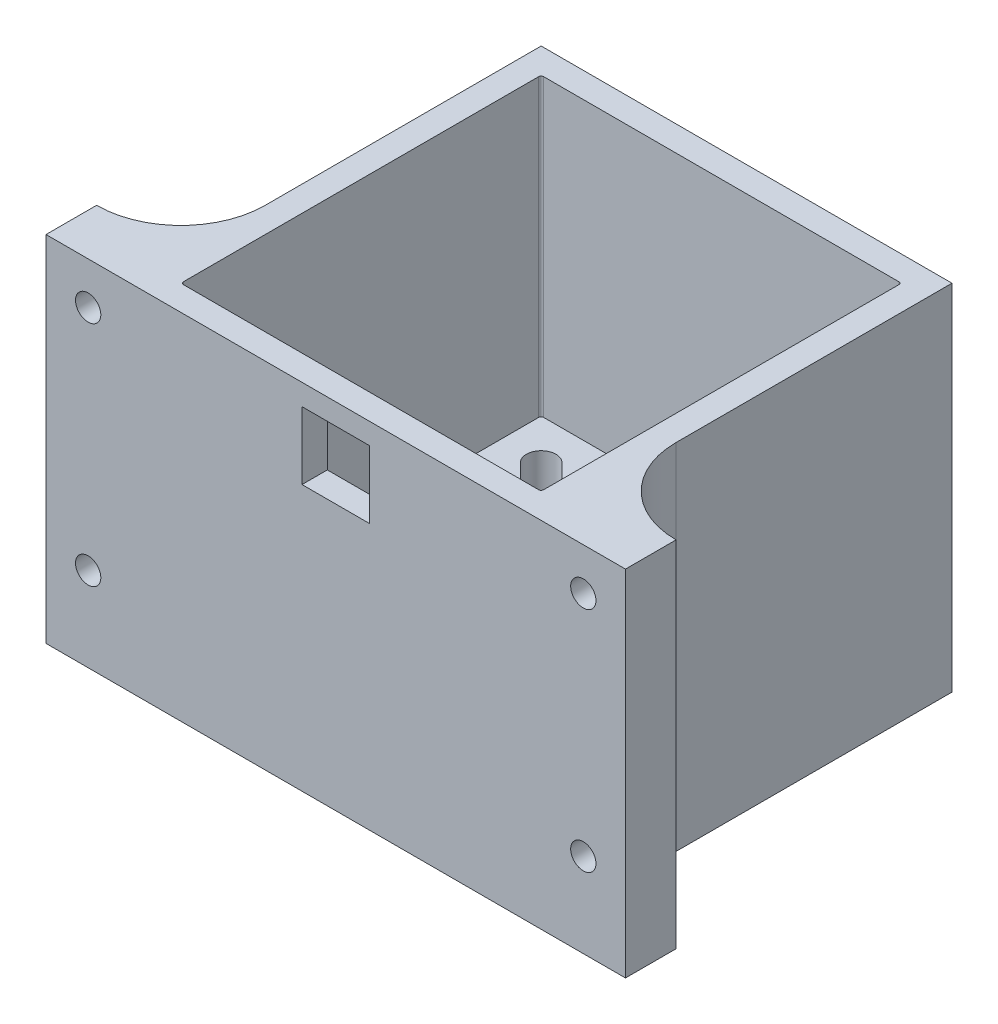
SolidWorks part; units mm, degrees
ref_plane "Front" through (0, 0, 0) normal (0, 0, 1) x (1, 0, 0)
ref_plane "Top" through (0, 0, 0) normal (0, 1, 0) x (1, 0, 0)
ref_plane "Right" through (0, 0, 0) normal (1, 0, 0) x (0, 0, -1)
sketch "Sketch1" plane through (0, 0, 0) normal (0, 1, 0) x (1, 0, 0)
  line L0 (-16.5607, 16.5607) -> (-14.4393, 14.4393) construction
  line L1 (-15.5, -15.5) -> (15.5, -15.5) construction
  line L2 (-15.5, -15.5) -> (-15.5, 15.5) construction
  line L3 (-15.5, 15.5) -> (15.5, 15.5) construction
  line L4 (15.5, -15.5) -> (15.5, 15.5) construction
  line L5 (-15.5, -15.5) -> (15.5, 15.5) construction
  line L6 (-15.5, 15.5) -> (15.5, -15.5) construction
  line L7 (-15.3232, 17.7981) -> (-13.2019, 15.6768)
  line L8 (-17.7981, 15.3232) -> (-15.6768, 13.2019)
  line L9 (0, 0) -> (0, 15.5) construction
  line L10 (0, 0) -> (15.5, 0) construction
  line L11 (16.5607, 16.5607) -> (14.4393, 14.4393) construction
  line L12 (15.3232, 17.7981) -> (13.2019, 15.6768)
  line L13 (17.7981, 15.3232) -> (15.6768, 13.2019)
  line L14 (16.5607, -16.5607) -> (14.4393, -14.4393) construction
  line L15 (15.3232, -17.7981) -> (13.2019, -15.6768)
  line L16 (17.7981, -15.3232) -> (15.6768, -13.2019)
  line L17 (-16.5607, -16.5607) -> (-14.4393, -14.4393) construction
  line L18 (-15.3232, -17.7981) -> (-13.2019, -15.6768)
  line L19 (-17.7981, -15.3232) -> (-15.6768, -13.2019)
  line L20 (21.0621, 21.3621) -> (21.3621, 21.3621) construction
  line L21 (-21.0621, -21.3621) -> (21.0621, -21.3621)
  line L22 (-21.3621, -21.0621) -> (-21.3621, 21.0621)
  line L23 (-21.0621, 21.3621) -> (21.0621, 21.3621)
  line L24 (21.3621, -21.0621) -> (21.3621, 21.0621)
  line L25 (21.3621, 21.3621) -> (21.3621, 21.0621) construction
  line L26 (-21.3621, 21.3621) -> (21.3621, -21.3621) construction
  line L27 (-21.15, -21.15) -> (21.15, -21.15) construction
  line L28 (-21.15, -21.15) -> (-21.15, 21.15) construction
  line L29 (-21.15, 21.15) -> (21.15, 21.15) construction
  line L30 (21.15, -21.15) -> (21.15, 21.15) construction
  line L31 (-21.15, -21.15) -> (21.15, 21.15) construction
  line L32 (-21.15, 21.15) -> (21.15, -21.15) construction
  line L33 (21.15, 21.15) -> (21.3621, 21.3621) construction
  line L34 (-24.3621, -21.0621) -> (-24.3621, 21.0621)
  line L35 (-21.0621, 24.3621) -> (21.0621, 24.3621)
  line L36 (24.3621, -21.0621) -> (24.3621, 21.0621)
  line L37 (-21.0621, -24.3621) -> (21.0621, -24.3621)
  line L38 (-24.3621, -21.0621) -> (-24.3621, -24.3621)
  line L39 (-24.3621, -24.3621) -> (-21.0621, -24.3621)
  line L40 (21.0621, -24.3621) -> (24.3621, -24.3621)
  line L41 (24.3621, -24.3621) -> (24.3621, -21.0621)
  line L42 (-24.3621, 21.0621) -> (-24.3621, 24.3621)
  line L43 (-24.3621, 24.3621) -> (-21.0621, 24.3621)
  line L44 (21.0621, 24.3621) -> (24.3621, 24.3621)
  line L45 (24.3621, 24.3621) -> (24.3621, 21.0621)
  arc A2 (-15.3232, 17.7981) -> (-17.7981, 15.3232) centre (-16.5607, 16.5607) ccw
  arc A3 (-15.6768, 13.2019) -> (-13.2019, 15.6768) centre (-14.4393, 14.4393) ccw
  arc A4 (15.3232, 17.7981) -> (17.7981, 15.3232) centre (16.5607, 16.5607) cw
  arc A5 (15.6768, 13.2019) -> (13.2019, 15.6768) centre (14.4393, 14.4393) cw
  arc A6 (15.3232, -17.7981) -> (17.7981, -15.3232) centre (16.5607, -16.5607) ccw
  arc A7 (15.6768, -13.2019) -> (13.2019, -15.6768) centre (14.4393, -14.4393) ccw
  arc A8 (-15.3232, -17.7981) -> (-17.7981, -15.3232) centre (-16.5607, -16.5607) cw
  arc A9 (-15.6768, -13.2019) -> (-13.2019, -15.6768) centre (-14.4393, -14.4393) cw
  arc A10 (21.3621, -21.0621) -> (21.0621, -21.3621) centre (21.0621, -21.0621) cw
  arc A11 (-21.0621, -21.3621) -> (-21.3621, -21.0621) centre (-21.0621, -21.0621) cw
  arc A12 (21.3621, 21.0621) -> (21.0621, 21.3621) centre (21.0621, 21.0621) ccw
  arc A13 (-21.0621, 21.3621) -> (-21.3621, 21.0621) centre (-21.0621, 21.0621) ccw
  arc A18 (-21.0621, -24.3621) -> (-24.3621, -21.0621) centre (-21.0621, -21.0621) cw construction
  arc A19 (24.3621, -21.0621) -> (21.0621, -24.3621) centre (21.0621, -21.0621) cw construction
  arc A20 (24.3621, 21.0621) -> (21.0621, 24.3621) centre (21.0621, 21.0621) ccw construction
  arc A21 (-21.0621, 24.3621) -> (-24.3621, 21.0621) centre (-21.0621, 21.0621) ccw construction
  point P0 (0, 0)
  point P9 (-15.5, 15.5)
  point P19 (15.5, 15.5)
  point P25 (15.5, -15.5)
  point P32 (-15.5, -15.5)
  dimension "D3" = 3.5
  dimension "D5" = 0.3
  dimension "D6" = 0.3
  dimension "D1" = 31
  dimension "D2" = 31
  dimension "D4" = 3
  dimension "D7" = 42.3
  dimension "D8" = 3
extrude "Boss-Extrude1" add sketch "Sketch1" along normal blind 7 contours L23 A13 L22 A11 L21 A10 L24 A12 L19 A9 L18 A8 L13 A5 L12 A4 A3 L8 A2 L7 A7 L16 A6 L15 | L37 L36 L35 L34 A13 L23 A12 L24 A10 L21 A11 L22 region at (0, 0, 0) region at (-23.6731, 0, 0)
sketch "Sketch2" plane through (0, 7, 0) normal (0, 1, 0) x (1, 0, 0)
  circle A0 centre (0, 0) radius 11
  dimension "D1" = 22
extrude "Cut-Extrude1" cut sketch "Sketch2" against normal blind 2
sketch "Sketch3" plane through (0, 5, 0) normal (0, 1, 0) x (1, 0, 0)
  circle A0 centre (0, 0) radius 5.5
  dimension "D1" = 11
extrude "Cut-Extrude2" cut sketch "Sketch3" against normal blind 4
sketch "Sketch4" plane through (0, 1, 0) normal (0, 1, 0) x (1, 0, 0)
  circle A0 centre (0, 0) radius 2.525
  dimension "D1" = 5.05
extrude "Cut-Extrude3" cut sketch "Sketch4" against normal through all
sketch "Sketch6" plane through (0, 7, 0) normal (0, 1, 0) x (1, 0, 0)
  line L0 (-21.0621, -21.3621) -> (21.0621, -21.3621) construction
  line L1 (-21.3621, -21.0621) -> (-21.3621, 21.0621) construction
  line L2 (-21.0621, 21.3621) -> (21.0621, 21.3621) construction
  line L3 (21.3621, -21.0621) -> (21.3621, 21.0621) construction
  line L4 (-21.0621, -21.3621) -> (21.0621, -21.3621)
  line L5 (-21.3621, -21.0621) -> (-21.3621, 21.0621)
  line L6 (-21.0621, 21.3621) -> (21.0621, 21.3621)
  line L7 (21.3621, -21.0621) -> (21.3621, 21.0621)
  line L12 (-24.3621, -24.3621) -> (24.3621, -24.3621)
  line L13 (24.3621, -24.3621) -> (24.3621, 24.3621)
  line L14 (24.3621, 24.3621) -> (-24.3621, 24.3621)
  line L15 (-24.3621, 24.3621) -> (-24.3621, -24.3621)
  line L16 (-24.3621, -24.3621) -> (24.3621, -24.3621)
  line L17 (24.3621, -24.3621) -> (24.3621, 24.3621)
  line L18 (24.3621, 24.3621) -> (-24.3621, 24.3621)
  line L19 (-24.3621, 24.3621) -> (-24.3621, -24.3621)
  arc A0 (-21.3621, -21.0621) -> (-21.0621, -21.3621) centre (-21.0621, -21.0621) ccw construction
  arc A1 (-21.0621, 21.3621) -> (-21.3621, 21.0621) centre (-21.0621, 21.0621) ccw construction
  arc A2 (21.3621, 21.0621) -> (21.0621, 21.3621) centre (21.0621, 21.0621) ccw construction
  arc A3 (21.0621, -21.3621) -> (21.3621, -21.0621) centre (21.0621, -21.0621) ccw construction
  arc A4 (-21.3621, -21.0621) -> (-21.0621, -21.3621) centre (-21.0621, -21.0621) ccw
  arc A5 (-21.0621, 21.3621) -> (-21.3621, 21.0621) centre (-21.0621, 21.0621) ccw
  arc A6 (21.3621, 21.0621) -> (21.0621, 21.3621) centre (21.0621, 21.0621) ccw
  arc A7 (21.0621, -21.3621) -> (21.3621, -21.0621) centre (21.0621, -21.0621) ccw
  dimension "D1" = 0
extrude "Boss-Extrude2" add sketch "Sketch6" along normal blind 35
sketch "Sketch8" plane through (0, 0, 24.3621) normal (0, 0, 1) x (1, 0, 0)
  line L0 (0, 31.5) -> (0, 0) construction
  line L1 (-4, 39.5) -> (4, 39.5)
  line L2 (-4, 39.5) -> (-4, 31.5)
  line L3 (-4, 31.5) -> (4, 31.5)
  line L4 (4, 39.5) -> (4, 31.5)
  line L5 (21.0621, 7) -> (-21.0621, 7) construction
  line L6 (21.0621, 7) -> (-21.0621, 7) construction
  line L7 (-24.3621, 42) -> (24.3621, 42) construction
  dimension "D1" = 2.5
  dimension "D2" = 8
extrude "Cut-Extrude4" cut sketch "Sketch8" against normal up to surface (3 mm away) up to face at (0, 24.5, 21.3621)
sketch "Sketch7" plane through (0, 0, 21.3621) normal (0, 0, 1) x (1, 0, 0)
  line L0 (21.0621, 7) -> (-21.0621, 7) construction
  line L1 (24.3621, 0) -> (-24.3621, 0) construction
  line L2 (24.3621, 0) -> (24.3621, 42) construction
  line L3 (24.3621, 42) -> (-24.3621, 42) construction
  line L4 (-24.3621, 0) -> (-24.3621, 42) construction
  line L5 (21.0621, 7) -> (-21.0621, 7) construction
  line L6 (-16.4192, 118.5607) -> (-14.2979, 116.4393) construction
  line L7 (24.3621, 42) -> (24.3621, 0) construction
  line L8 (-24.3621, 42) -> (24.3621, 42)
  line L9 (-24.3621, 42) -> (-24.3621, 102) construction
  line L10 (-24.3621, 102) -> (24.3621, 102) construction
  line L11 (24.3621, 42) -> (24.3621, 102) construction
  line L12 (-24.3621, 42) -> (-24.3621, 0) construction
  line L13 (-24.3621, 0) -> (24.3621, 0) construction
  line L14 (-15.3586, 86.5) -> (15.6414, 86.5) construction
  line L15 (-15.3586, 86.5) -> (-15.3586, 117.5) construction
  line L16 (-15.3586, 117.5) -> (15.6414, 117.5) construction
  line L17 (15.6414, 86.5) -> (15.6414, 117.5) construction
  line L18 (-15.3586, 86.5) -> (15.6414, 117.5) construction
  line L19 (-15.3586, 117.5) -> (15.6414, 86.5) construction
  line L20 (-15.1818, 119.7981) -> (-13.0605, 117.6768)
  line L21 (-17.6567, 117.3232) -> (-15.5354, 115.2019)
  line L22 (0.1414, 102) -> (0.1414, 117.5) construction
  line L23 (0.1414, 102) -> (15.6414, 102) construction
  line L24 (16.7021, 118.5607) -> (14.5808, 116.4393) construction
  line L25 (15.4646, 119.7981) -> (13.3433, 117.6768)
  line L26 (17.9395, 117.3232) -> (15.8182, 115.2019)
  line L27 (16.7021, 85.4393) -> (14.5808, 87.5607) construction
  line L28 (15.4646, 84.2019) -> (13.3433, 86.3232)
  line L29 (17.9395, 86.6768) -> (15.8182, 88.7981)
  line L30 (-16.4192, 85.4393) -> (-14.2979, 87.5607) construction
  line L31 (-15.1818, 84.2019) -> (-13.0605, 86.3232)
  line L32 (-17.6567, 86.6768) -> (-15.5354, 88.7981)
  line L33 (21.145, 123.5036) -> (21.645, 123.5036) construction
  line L34 (-20.8621, 80.4964) -> (21.145, 80.4964)
  line L35 (-21.3621, 80.9964) -> (-21.3621, 123.0036)
  line L36 (-20.8621, 123.5036) -> (21.145, 123.5036)
  line L37 (21.645, 80.9964) -> (21.645, 123.0036)
  line L38 (21.645, 123.5036) -> (21.645, 123.0036) construction
  line L39 (-21.3621, 123.5036) -> (21.645, 80.4964) construction
  line L40 (-21.0086, 80.85) -> (21.2914, 80.85) construction
  line L41 (-21.0086, 80.85) -> (-21.0086, 123.15) construction
  line L42 (-21.0086, 123.15) -> (21.2914, 123.15) construction
  line L43 (21.2914, 80.85) -> (21.2914, 123.15) construction
  line L44 (-21.0086, 80.85) -> (21.2914, 123.15) construction
  line L45 (-21.0086, 123.15) -> (21.2914, 80.85) construction
  line L46 (21.2914, 123.15) -> (21.645, 123.5036) construction
  line L60 (-24.3621, 77.4964) -> (24.645, 77.4964)
  line L61 (-24.3621, 77.4964) -> (-24.3621, 126.5036)
  line L62 (-24.3621, 126.5036) -> (24.645, 126.5036)
  line L63 (24.645, 77.4964) -> (24.645, 126.5036)
  line L64 (-24.3621, 77.4964) -> (24.645, 126.5036) construction
  line L65 (-24.3621, 126.5036) -> (24.645, 77.4964) construction
  line L66 (-24.3621, 77.4964) -> (24.3621, 77.4964)
  line L67 (-24.3621, 77.4964) -> (-24.3621, 42)
  line L68 (-24.3621, 42) -> (24.3621, 42)
  line L69 (24.3621, 77.4964) -> (24.3621, 42)
  arc A0 (-15.1818, 119.7981) -> (-17.6567, 117.3232) centre (-16.4192, 118.5607) ccw
  arc A1 (-15.5354, 115.2019) -> (-13.0605, 117.6768) centre (-14.2979, 116.4393) ccw
  arc A2 (15.4646, 119.7981) -> (17.9395, 117.3232) centre (16.7021, 118.5607) cw
  arc A3 (15.8182, 115.2019) -> (13.3433, 117.6768) centre (14.5808, 116.4393) cw
  arc A4 (15.4646, 84.2019) -> (17.9395, 86.6768) centre (16.7021, 85.4393) ccw
  arc A5 (15.8182, 88.7981) -> (13.3433, 86.3232) centre (14.5808, 87.5607) ccw
  arc A6 (-15.1818, 84.2019) -> (-17.6567, 86.6768) centre (-16.4192, 85.4393) cw
  arc A7 (-15.5354, 88.7981) -> (-13.0605, 86.3232) centre (-14.2979, 87.5607) cw
  arc A8 (21.645, 80.9964) -> (21.145, 80.4964) centre (21.145, 80.9964) cw
  arc A9 (-20.8621, 80.4964) -> (-21.3621, 80.9964) centre (-20.8621, 80.9964) cw
  arc A10 (21.645, 123.0036) -> (21.145, 123.5036) centre (21.145, 123.0036) ccw
  arc A11 (-20.8621, 123.5036) -> (-21.3621, 123.0036) centre (-20.8621, 123.0036) ccw
  point P6 (0.1414, 102)
  point P23 (-15.3586, 117.5)
  point P33 (15.6414, 117.5)
  point P39 (15.6414, 86.5)
  point P46 (-15.3586, 86.5)
  dimension "D7" = 0.5
  dimension "D1" = 35
  dimension "D2" = 60
  dimension "D3" = 31
  dimension "D4" = 31
  dimension "D5" = 3.5
  dimension "D6" = 3
  dimension "D8" = 42.3
  dimension "D9" = 0.5
  dimension "D10" = 3
sketch "Sketch9" plane through (0, 0, 24.3621) normal (0, 0, 1) x (1, 0, 0)
  line L1 (24.3621, 42) -> (34.3621, 42)
  line L2 (24.3621, 42) -> (24.3621, 32)
  line L3 (24.3621, 32) -> (34.3621, 32) construction
  line L4 (34.3621, 42) -> (34.3621, 32)
  line L5 (24.3621, 15) -> (34.3621, 15) construction
  line L6 (24.3621, 15) -> (24.3621, 5)
  line L7 (24.3621, 5) -> (34.3621, 5) construction
  line L8 (34.3621, 15) -> (34.3621, 5)
  line L9 (24.3621, 32) -> (24.3621, 15)
  line L10 (34.3621, 15) -> (34.3621, 32)
  line L11 (0, 0) -> (0, 42) construction
  line L12 (-24.3621, 0) -> (24.3621, 0) construction
  line L13 (-24.3621, 42) -> (24.3621, 42) construction
  line L14 (24.3621, 0) -> (34.3621, 0)
  line L15 (34.3621, 0) -> (34.3621, 5)
  circle A0 centre (29.3621, 37) radius 1.5
  circle A1 centre (29.3621, 10) radius 1.5
  point P9 (34.3621, 37)
  point P12 (29.3621, 42)
  point P18 (34.3621, 10)
  line M12 (24.3621, 0) -> (24.3621, 42)
  dimension "D1" = 3
  dimension "D2" = 10
  dimension "D3" = 5
extrude "Boss-Extrude4" add sketch "Sketch9" against normal blind 6 contours L14 L15 L8 L10 L4 L1 A1 A0 M12 region at (29.3621, 20.9129, 24.3621)
mirror "Mirror1" about plane through (0, 0, 0) normal (1, 0, 0) of "Boss-Extrude4"
fillet "Fillet1" radius 10 2 edges at (-24.3621, 21, 18.3621) (24.3621, 21, 18.3621)
ref_plane "Plane1" through (0, 0, 14.3621) normal (0, 0, 1) x (1, 0, 0)
sketch "Sketch10" plane through (0, 0, 14.3621) normal (0, 0, 1) x (1, 0, 0)
  circle A0 centre (-29.3621, 37) radius 2.5
  circle A1 centre (-29.3621, 10) radius 2.5
  circle A2 centre (29.3621, 37) radius 2.5
  circle A3 centre (29.3621, 10) radius 2.5
  dimension "D1" = 5
extrude "Cut-Extrude5" cut sketch "Sketch10" along normal blind 7
